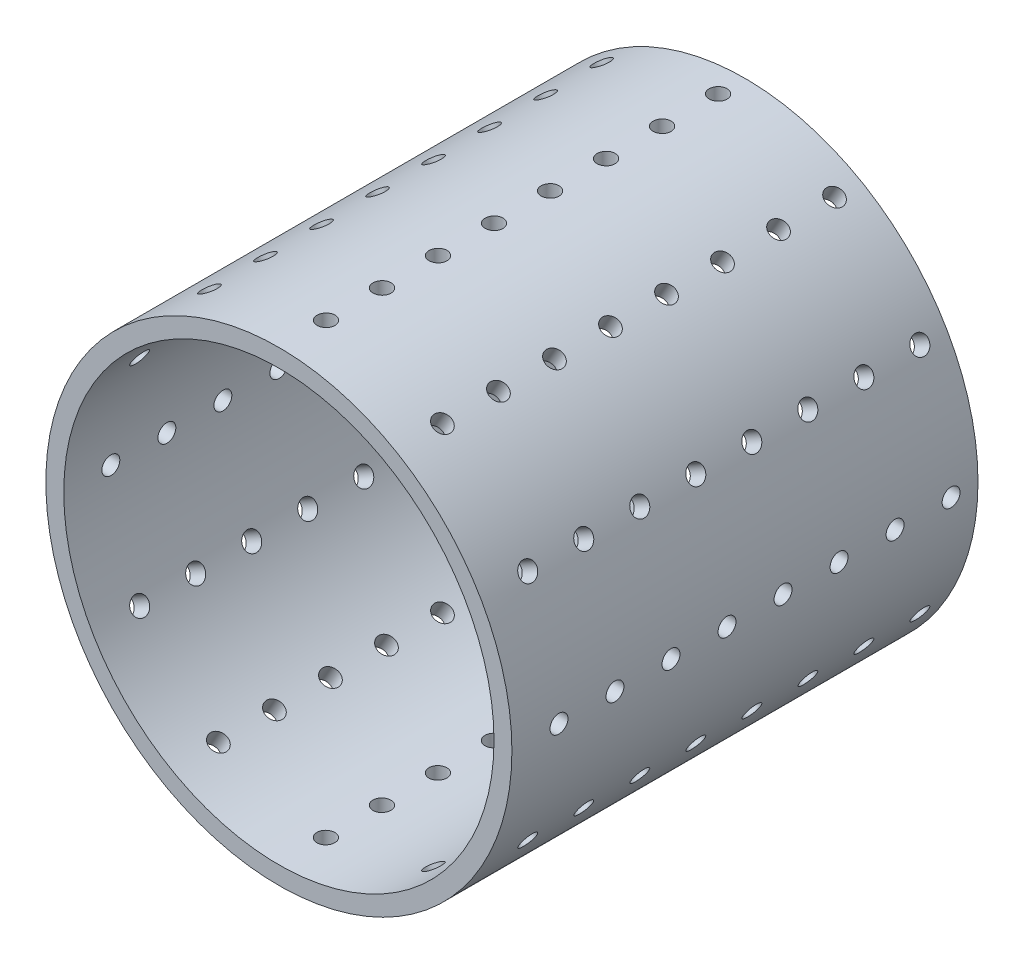
SolidWorks part; units mm, degrees
material "PVC 0.007 Plasticized"
ref_plane "Front" through (0, 0, 0) normal (0, 0, 1) x (1, 0, 0)
ref_plane "Top" through (0, 0, 0) normal (0, 1, 0) x (1, 0, 0)
ref_plane "Right" through (0, 0, 0) normal (1, 0, 0) x (0, 0, -1)
sketch "Sketch1" plane through (0, 0, 0) normal (0, 0, 1) x (1, 0, 0)
  line L0 (0, 38.1) -> (0, 41.275)
  circle A0 centre (0, 0) radius 38.1
  circle A1 centre (0, 0) radius 41.275
extrude "Boss-Extrude1" add sketch "Sketch1" along normal blind 82.55 contours A1 A0 region at (28.3603, 28.3603, 0)
sketch "Sketch2" plane through (0, 0, 0) normal (0, 1, 0) x (1, 0, 0)
  line L2 (0, -44.45) -> (-0.5167, -44.6342)
  circle A0 centre (0, -44.45) radius 1.5875
  circle A1 centre (0, -4.7625) radius 1.5875
  circle A2 centre (0, -84.1375) radius 1.5875
  circle A3 centre (0, -24.6062) radius 1.5875
  circle A4 centre (0, -64.2938) radius 1.5875
  circle A5 centre (0, -14.6844) radius 1.5875
  circle A6 centre (0, -34.5281) radius 1.5875
  circle A7 centre (0, -54.3719) radius 1.5875
  circle A8 centre (0, -74.2156) radius 1.5875
extrude "Cut-Extrude2" cut sketch "Sketch2" against normal mid plane 88.9 contours A1 | A5 | A3 | A6 | A0 | A7 | A4 | A8 | A2
pattern_circular "CirPattern1" count 12 every 30 about axis through (0, 0, 82.55) along (0, 0, -1) of "Cut-Extrude2"
